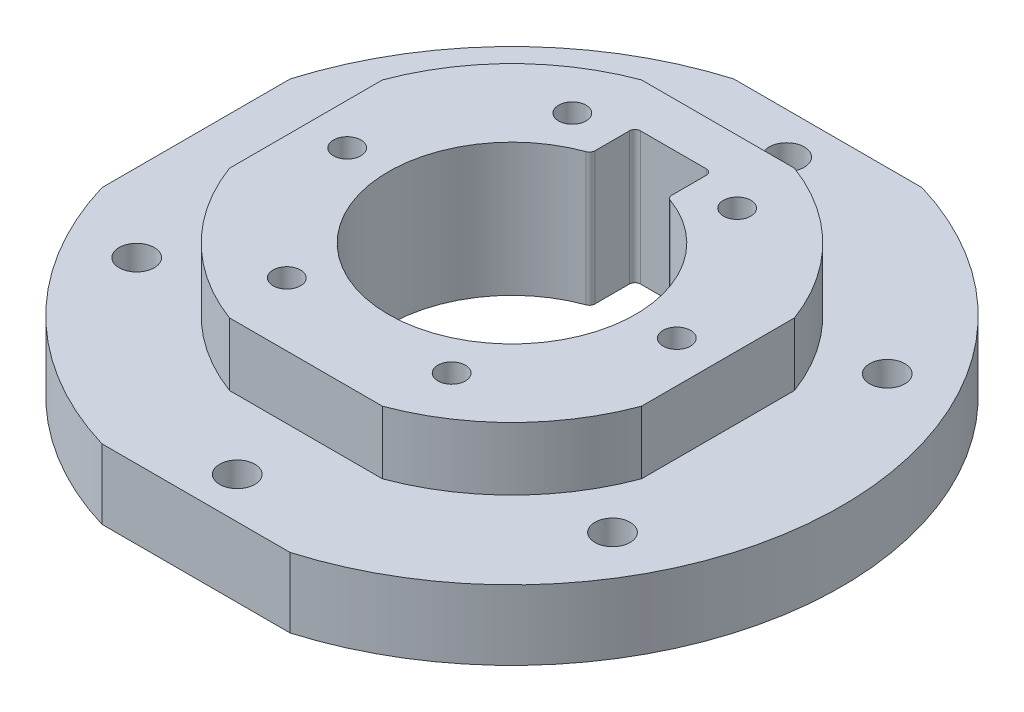
SolidWorks part; units mm, degrees
note: The reader was unsure of these and kept them because the rebuilt part matched: shared geometry of "Sketch1<7>".
material "6061 Alloy"
ref_plane "Front Plane" through (0, 0, 0) normal (0, 0, 1) x (1, 0, 0)
ref_plane "Top Plane" through (0, 0, 0) normal (0, 1, 0) x (1, 0, 0)
ref_plane "Right Plane" through (0, 0, 0) normal (1, 0, 0) x (0, 0, -1)
sketch "Sketch1" plane through (0, 0, 0) normal (0, 1, 0) x (1, 0, 0)
  line L0 (-7.5664, 10.2) -> (7.5664, 10.2) construction
  line L1 (-7.5664, -10.2) -> (7.5664, -10.2) construction
  line L2 (-7, 21.3834) -> (-7, 29.3834)
  line L3 (-7, 29.3834) -> (7, 29.3834)
  line L4 (7, 29.3834) -> (7, 21.3834)
  line L5 (-13.9194, 37.5) -> (13.9194, 37.5)
  line L6 (-37.5, 13.9194) -> (-37.5, -13.9194)
  line L7 (-13.9194, -37.5) -> (13.9194, -37.5)
  line L8 (37.5, 13.9194) -> (37.5, -13.9194)
  line L9 (-17.1391, 57.5) -> (17.1391, 57.5)
  line L10 (-57.5, 17.1391) -> (-57.5, -17.1391)
  line L11 (-17.1391, -57.5) -> (17.1391, -57.5)
  line L12 (57.5, 17.1391) -> (57.5, -17.1391)
  arc A0 (-7.5664, 10.2) -> (-7.5664, -10.2) centre (0, 0) ccw construction
  arc A1 (7.5664, -10.2) -> (7.5664, 10.2) centre (0, 0) ccw construction
  circle A2 centre (0, 0) radius 60
  circle A3 centre (0, 0) radius 30 construction
  circle A4 centre (-30, 0) radius 3 construction
  circle A5 centre (-15, 25.9808) radius 3 construction
  circle A6 centre (15, 25.9808) radius 3 construction
  circle A7 centre (30, 0) radius 3 construction
  circle A8 centre (15, -25.9808) radius 3 construction
  circle A9 centre (-15, -25.9808) radius 3 construction
  circle A10 centre (0, 0) radius 22.5
  circle A11 centre (0, 0) radius 50 construction
  circle A12 centre (0, 50) radius 3 construction
  circle A13 centre (43.3013, 25) radius 3 construction
  circle A14 centre (43.3013, -25) radius 3 construction
  circle A15 centre (0, -50) radius 3 construction
  circle A16 centre (-43.3013, -25) radius 3 construction
  circle A17 centre (-43.3013, 25) radius 3 construction
  circle A18 centre (0, 0) radius 40
  point P19 (0, 0)
  point P38 (0, 0)
  dimension "D1" = 12.7
  dimension "D3" = 120
  dimension "D4" = 60
  dimension "D6" = 6
  dimension "D7" = 45
  dimension "D8" = 6
  dimension "D9" = 100
  dimension "D12" = 80
  dimension "D2" = 20.4
  dimension "D10" = 14
  dimension "D11" = 8
  dimension "D13" = 75
  dimension "D14" = 115
  dimension "D5" = 6
extrude "Boss-Extrude1" add sketch "Sketch1" against normal blind 12.7
hole_wizard "M6 Clearance Hole1" positions "3DSketch2" profile "Sketch3" hole size "M6" standard "ANSI Metric" end condition up to next
sketch3d "3DSketch2"
  point P0 (-43.3013, 0, 25)
  point P7 (0, 0, -50)
  point P9 (43.3013, 0, -25)
  point P11 (43.3013, 0, 25)
  point P13 (0, 0, 50)
  point P15 (-43.3013, 0, -25)
sketch "Sketch3" plane through (-43.3013, 0, 25) normal (1, 0, 0) x (0, 0, 1)
  line L0 (0, 0) -> (0, 12.7)
  line L1 (0, 12.7) -> (3.2, 12.7)
  line L2 (3.2, 12.7) -> (3.2, 0)
  line L5 (3.2, 0) -> (0, 0)
  line L11 (0, -6.35) -> (0, 107.95) construction
  dimension "Thru Hole Dia." = 6.4
  dimension "Thru Hole Depth" = 12.7
extrude "Boss-Extrude2" add sketch "Sketch1<7>" along normal blind 11.45 contours L7 A18 L8 L5 L6 A10 L2 L3 L4
sketch "Sketch1<7>" plane through (0, 0, 0) normal (0, 1, 0) x (1, 0, 0) same geometry as "Sketch1"
hole_wizard "Tap Drill for M6x1.0 Tap1" positions "3DSketch1" profile "Sketch2" hole size "M6x1.0" standard "ANSI Metric"
sketch3d "3DSketch1"
  point P0 (-30, 0, 0)
  point P2 (-15, 0, -25.9808)
  point P4 (15, 0, -25.9808)
  point P6 (30, 0, 0)
  point P8 (15, 0, 25.9808)
  point P10 (-15, 0, 25.9808)
sketch "Sketch2" plane through (-30, 0, 0) normal (1, 0, 0) x (0, 0, 1)
  line L0 (0, 0) -> (0, 12.7)
  line L1 (0, 12.7) -> (2.5, 12.7)
  line L2 (2.5, 12.7) -> (2.5, 0)
  line L5 (2.5, 0) -> (0, 0)
  line L11 (0, -6.35) -> (0, 107.95) construction
  dimension "Thru Hole Dia." = 5
  dimension "Thru Hole Depth" = 12.7
hole_wizard "Tap Drill for M6x1.0 Tap3" positions "3DSketch4" profile "Sketch5" hole size "M6x1.0" standard "ANSI Metric" end condition up to next
sketch3d "3DSketch4"
  point P0 (30, 0, 0)
  point P2 (-15, 0, -25.9808)
  point P4 (15, 0, 25.9808)
  point P6 (-30, 0, 0)
  point P8 (-15, 0, 25.9808)
  point P10 (15, 0, -25.9808)
sketch "Sketch5" plane through (30, 0, 0) normal (1, 0, 0) x (0, 0, -1)
  line L0 (0, 0) -> (0, 11.45)
  line L1 (0, 11.45) -> (2.5, 11.45)
  line L2 (2.5, 11.45) -> (2.5, 0)
  line L5 (2.5, 0) -> (0, 0)
  line L11 (0, -6.35) -> (0, 107.95) construction
  dimension "Thru Hole Dia." = 5
  dimension "Thru Hole Depth" = 11.45
fillet "Fillet1" radius 1 4 edges at (7, -0.625, -29.3834) (-7, -0.625, -29.3834) (7, -0.625, -21.3834) (-7, -0.625, -21.3834)
